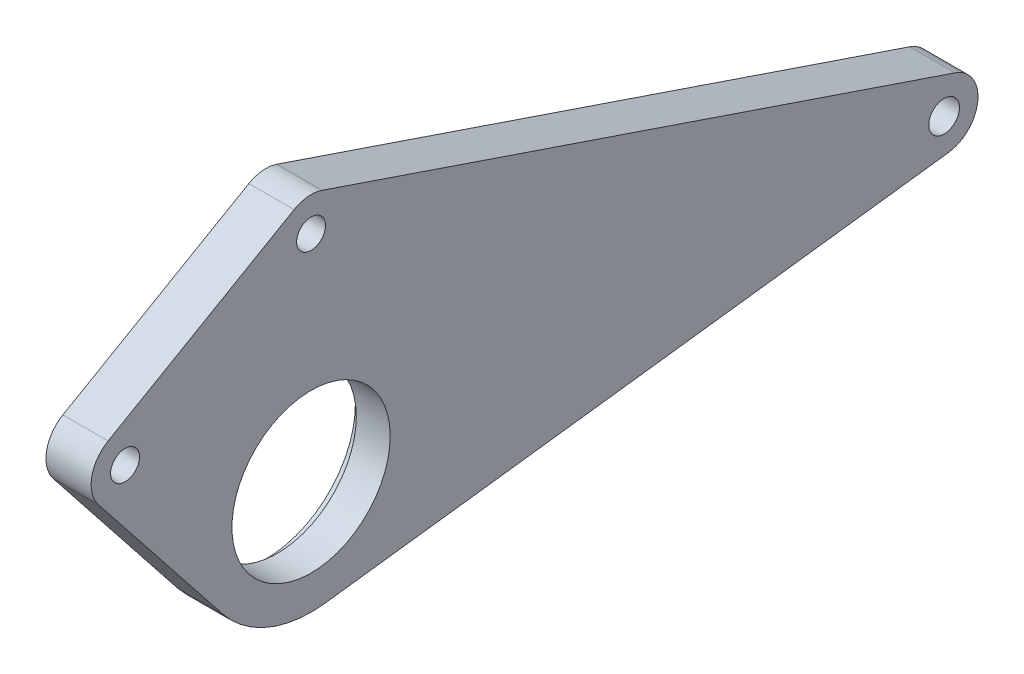
SolidWorks part; units mm, degrees
ref_plane "Front Plane" through (0, 0, 0) normal (0, 0, 1) x (1, 0, 0)
ref_plane "Top Plane" through (0, 0, 0) normal (0, 1, 0) x (1, 0, 0)
ref_plane "Right Plane" through (0, 0, 0) normal (1, 0, 0) x (0, 0, -1)
sketch "Sketch1" plane through (0, 0, 0) normal (1, 0, 0) x (0, 0, -1)
  line L0 (1.5302, 4.51) -> (-87.3698, 34.6725)
  line L1 (-91.2812, 34.2869) -> (-117.4027, 19.2057)
  line L2 (-118.7548, 12.1242) -> (-101.3443, -9.8568)
  line L3 (-86.9156, -15.7505) -> (0.5953, -4.7251)
  line L4 (-115.0215, 15.0813) -> (-88.9, 0) construction
  line L5 (-88.9, 0) -> (-88.9, 30.1625) construction
  line L6 (0, 0) -> (-88.9, 0) construction
  circle A0 centre (0, 0) radius 2.159
  arc A1 (0.5953, -4.7251) -> (1.5302, 4.51) centre (0, 0) ccw
  arc A2 (-87.3698, 34.6725) -> (-91.2812, 34.2869) centre (-88.9, 30.1625) ccw
  arc A3 (-117.4027, 19.2057) -> (-118.7548, 12.1242) centre (-115.0215, 15.0813) ccw
  arc A4 (-101.3443, -9.8568) -> (-86.9156, -15.7505) centre (-88.9, 0) ccw
  circle A5 centre (-88.9, 0) radius 11.1125
  circle A6 centre (-88.9, 30.1625) radius 2.032
  circle A7 centre (-88.9, 0) radius 25.4 construction
  circle A8 centre (-115.0215, 15.0813) radius 2.032
  dimension "D1" = 4.318
  dimension "D2" = 9.525
  dimension "D3" = 22.225
  dimension "D4" = 4.7625
  dimension "D5" = 15.875
  dimension "D6" = 50.8
  dimension "D10" = 4.064
  dimension "D7" = 30.1625
  dimension "D8" = 88.9
  dimension "D9" = 60
extrude "Boss-Extrude1" add sketch "Sketch1" along normal blind 6.35
sketch "Sketch2" plane through (6.35, 0, 0) normal (1, 0, 0) x (0, 0, -1)
  circle A0 centre (-88.9, 0) radius 12.573
  dimension "D1" = 25.146
extrude "Cut-Extrude1" cut sketch "Sketch2" against normal blind 1.5875
mirror "Mirror1" about plane through (6.35, 0, 0) normal (1, 0, 0) of bodies 102
delete or keep bodies "Body-Delete/Keep 1" type delete bodies bodies 102
